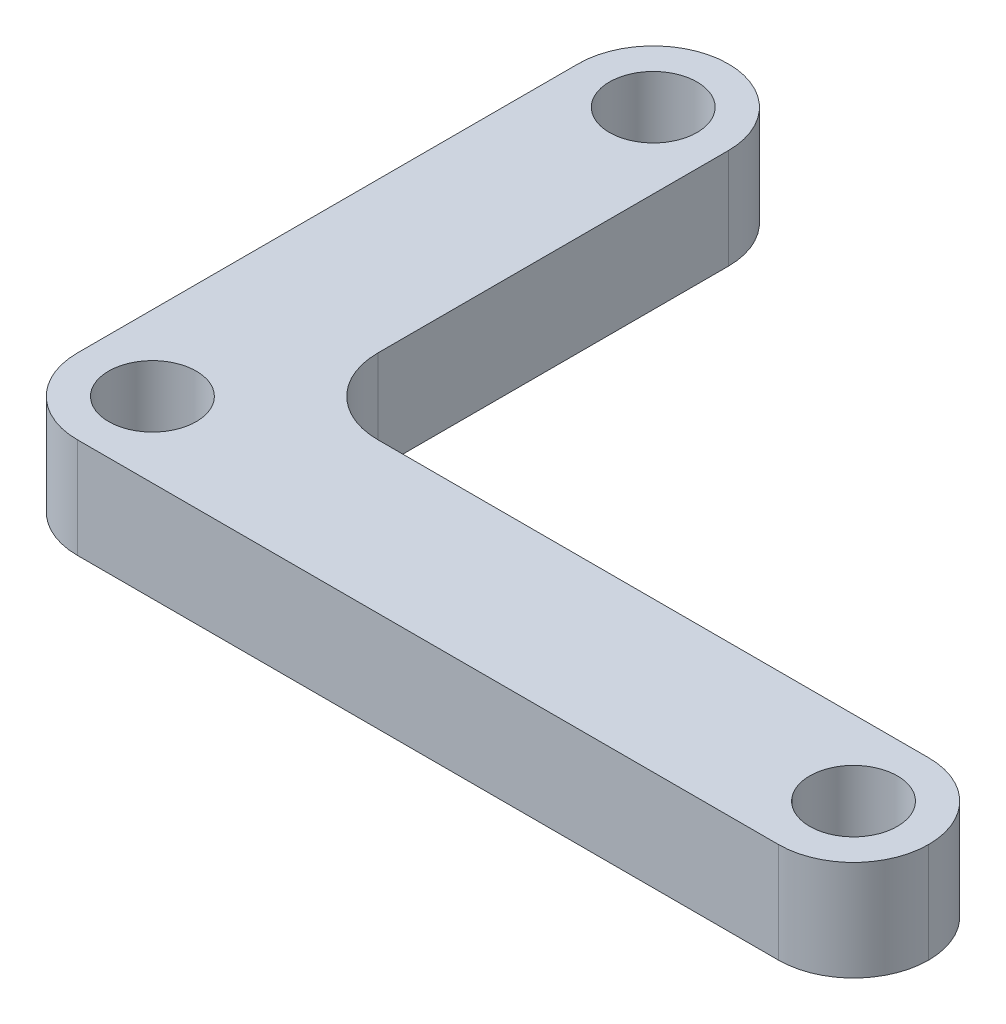
SolidWorks part; units mm, degrees
ref_plane "Alzado" through (0, 0, 0) normal (0, 0, 1) x (1, 0, 0)
ref_plane "Planta" through (0, 0, 0) normal (0, 1, 0) x (1, 0, 0)
ref_plane "Vista lateral" through (0, 0, 0) normal (1, 0, 0) x (0, 0, -1)
sketch "Croquis1" plane through (0, 0, 0) normal (0, 1, 0) x (1, 0, 0)
  line L0 (0, 0) -> (0, 26)
  line L1 (0, 26) -> (6, 26)
  line L2 (6, 26) -> (6, 6)
  line L3 (6, 6) -> (34, 6)
  line L4 (34, 6) -> (34, 0)
  line L5 (34, 0) -> (0, 0)
  line L6 (3, 26) -> (3, 0) construction
  line L7 (34, 3) -> (0, 3) construction
  circle A0 centre (3, 23) radius 1.75
  circle A1 centre (31, 3) radius 1.75
  circle A2 centre (3, 3) radius 1.75
  dimension "D3" = 3.5
  dimension "D4" = 3.5
  dimension "D5" = 3.5
  dimension "D1" = 6
  dimension "D2" = 6
  dimension "D6" = 3
  dimension "D7" = 3
  dimension "D8" = 28
  dimension "D9" = 20
extrude "Saliente-Extruir1" add sketch "Croquis1" along normal blind 4
fillet "Redondeo1" radius 3 6 edges at (6, 2, -6) (0, 2, 0) (0, 2, -26) (6, 2, -26) (34, 2, -6) (34, 2, 0)
